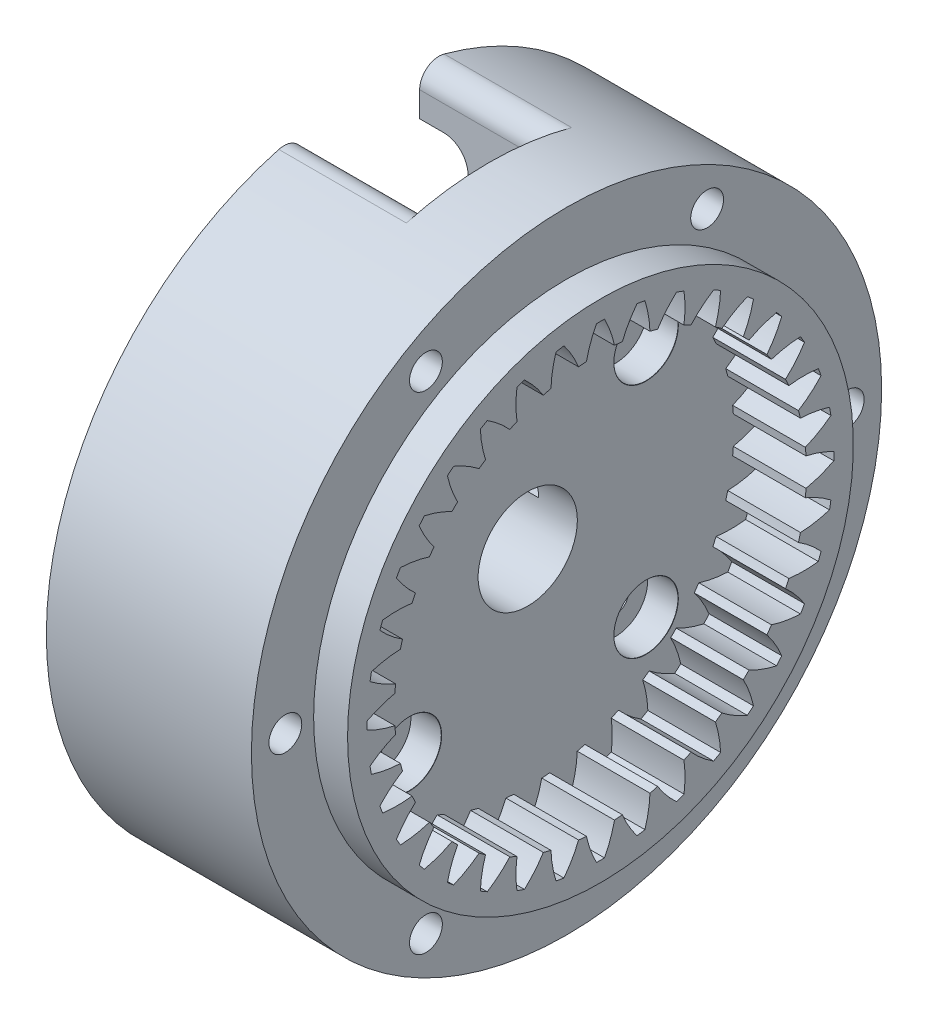
SolidWorks part; units mm, degrees
other "Markup1"
sketch "Sketch48"
ref_plane "Plane1" through (0, 0, 0) normal (0, 0, 1) x (1, 0, 0)
ref_plane "Plane2" through (0, 0, 0) normal (0, 1, 0) x (1, 0, 0)
ref_plane "Plane3" through (0, 0, 0) normal (1, 0, 0) x (0, 0, -1)
sketch "HoldingSke" plane through (0, 0, 0) normal (0, 1, 0) x (1, 0, 0)
  line L0 (0, 0) -> (328.7845, -238.8759)
  line L1 (-15, 0) -> (100, 0) construction
  line L2 (0, 0) -> (-2.1039, 2.3779)
  line L3 (0, 0) -> (-11.863, 4.5341)
  line L4 (0, 0) -> (6.9867, 5.0761)
  line L5 (0, 0) -> (-23.7986, -8.8762)
  line L6 (0, 0) -> (-10.5278, -7.1032)
  line L7 (-2.1039, 2.3779) -> (3.3635, 27.1825)
  line L8 (-76.2, 54.61) -> (-54.61, 54.61)
  line L9 (-67.7845, 28.3722) -> (-49.3413, 33.142)
  line L10 (-76.2, 71.12) -> (104.1128, 71.12)
  line L11 (0, 0) -> (-9.525, 0)
  line L12 (-76.2, 101.6) -> (-76.1428, 101.6)
  line L13 (24.9733, 27.94) -> (52.9518, 28.4284)
  line L14 (24.9733, 27.94) -> (24.9746, 27.94)
  line L15 (24.9733, 27.94) -> (100.4006, 29.5858)
  circle A0 centre (0, 0) radius 12.7
  circle A1 centre (0, 0) radius 12.7
  circle A2 centre (0, 0) radius 12.7
  dimension "MHD" = 25.4
  dimension "Hub_dia" = 25.4
  dimension "Diameter" = 25.4
  dimension "Num_teeth" = 36
  dimension "Pitch" = 406.4
  dimension "Overall_len" = 25.4
  dimension "Show_teeth" = 36
  dimension "Thickness" = 12.7
  dimension "OAL" = 25.4001
  dimension "T_dim" = 21.59
  dimension "Ap" = 14.5
  dimension "H" = 19.05
  dimension "Pitch_radius" = 180.3128
  dimension "Width" = 9.525
  dimension "Backlash" = 0.0571
  dimension "Addendum_fac" = 1
  dimension "Dedendum_fac" = 1.25
  dimension "Clearance_fac" = 0.25
  dimension "Dedendum_add" = 0.0013
sketch "BasProSke" plane through (0, 0, 0) normal (0, 1, 0) x (1, 0, 0)
  line L0 (-10, 0) -> (60, 0) construction
  line L1 (0, 26.9875) -> (0, 30.586)
  line L2 (0, 26.9875) -> (9.525, 26.9875)
  line L3 (9.525, 26.9875) -> (9.525, 30.586)
  line L4 (9.525, 30.586) -> (0, 30.586)
  dimension "Thickness" = 9.525
  dimension "Diameter" = 61.1721
  dimension "Inside_diameter" = 53.975
revolve "Base-Revolve" add sketch "BasProSke" angle 360 about L0
sketch "TooCutSke" plane through (0, 0, 0) normal (1, 0, 0) x (0, 0, -1)
  line L3 (1.3893, 28.5412) -> (1.3893, 53.6633) construction
  line L4 (0, 0) -> (0, 59.563) construction
  line L5 (0, 0) -> (-5.9551, 68.0675) construction
  line L6 (-12.1342, 23.9318) -> (35.5288, 28.1018) construction
  circle A0 centre (0, 0) radius 28.575 construction
  circle A1 centre (0, 0) radius 30.5606 construction
  circle A2 centre (0, 0) radius 24.8983 construction
  circle A3 centre (0, 0) radius 26.9621 construction
  arc A4 (1.8417, 26.8991) -> (0.5248, 30.5561) centre (-12.1342, 23.9318) ccw
  arc A5 (1.8417, 26.8991) -> (-1.8417, 26.8991) centre (0, 0) ccw
  arc A6 (0.5248, 30.5561) -> (-0.5248, 30.5561) centre (0, 0) ccw
  arc A7 (-0.5248, 30.5561) -> (-1.8417, 26.8991) centre (12.1342, 23.9318) ccw
  dimension "Pitch_dia" = 57.15
  dimension "Base_dia" = 49.7967
  dimension "Root_dia" = 61.1213
  dimension "Overcut_dia" = 53.9242
  dimension "Flank_rad" = 14.2875
  dimension "Half_ang" = 5
  dimension "Half_CT" = 1.3893
extrude "ToothCut" cut sketch "TooCutSke" along normal through all
fillet "Breaks" [suppressed] radius 0.1588
fillet "RootFillets" [suppressed] radius 0.3981
pattern_circular "TeethCuts" count 36 over 360 about axis through (0, 0, 0) along (1, 0, 0) of "RootFillets", "Breaks", "ToothCut"
sketch "Sketch3" plane through (0, 0, 0) normal (1, 0, 0) x (0, 0, -1)
  circle A0 centre (0, 0) radius 30.586 construction
  circle A1 centre (0, 0) radius 30.586
extrude "Extrude-Thin1" add sketch "Sketch3" along normal up to surface (9.525 mm away) thin
sketch "Sketch4" plane through (0, 0, 0) normal (1, 0, 0) x (0, 0, -1)
  circle A0 centre (0, 0) radius 33.126 construction
  circle A1 centre (0, 0) radius 33.126
extrude "Extrude-Thin2" add sketch "Sketch4" along normal blind 5.08 thin
sketch "Sketch5" plane through (0, 0, 0) normal (1, 0, 0) x (0, 0, -1)
  circle A0 centre (0, 0) radius 28.575 construction
  dimension "D1" = 57.15
sketch "Sketch9" plane through (0, 0, 0) normal (-1, 0, 0) x (0, 0, 1)
  circle A0 centre (0, 0) radius 59.944
  circle A1 centre (0, 0) radius 39.476 construction
  circle A2 centre (0, 0) radius 39.476
  dimension "D1" = 119.888
extrude "Boss-Extrude2" add sketch "Sketch9" against normal up to surface (5.08 mm away) up to face at (5.08, 0, -39.476)
sketch "Sketch12" plane through (0, 0, 0) normal (-1, 0, 0) x (0, 0, 1)
  circle A1 centre (0, 0) radius 59.944
  circle A5 centre (0, 0) radius 59.944
  dimension "D1" = 0
extrude "Boss-Extrude3" add sketch "Sketch12" along normal blind 5.08 contours A5
sketch "Sketch13" plane through (0, 0, 0) normal (1, 0, 0) x (0, 0, -1)
  circle A0 centre (0, 0) radius 20.2565
  circle A1 centre (0, 0) radius 17.9705
  dimension "D1" = 40.513
  dimension "D2" = 35.941
extrude "Cut-Extrude10" cut sketch "Sketch13" against normal blind 2.032
sketch "Sketch14" plane through (-5.08, 0, 0) normal (-1, 0, 0) x (0, 0, 1)
  circle A0 centre (0, 0) radius 3.302
  dimension "D1" = 6.604
extrude "Cut-Extrude11" cut sketch "Sketch14" against normal through all both and the other way through all
sketch "Sketch15" plane through (5.08, 0, 0) normal (1, 0, 0) x (0, 0, -1)
  circle A0 centre (0, 0) radius 47.498
  circle A1 centre (0, 0) radius 59.944 construction
  circle A2 centre (0, 0) radius 59.944
  dimension "D1" = 12.446
extrude "Boss-Extrude5" add sketch "Sketch15" along normal blind 14.605
sketch "Sketch16" plane through (19.685, 0, 0) normal (1, 0, 0) x (0, 0, -1)
  line L0 (0, 56.388) -> (0, 59.944) construction
  line L1 (0, 51.308) -> (0, 47.498) construction
  line L2 (56.388, 0) -> (59.944, 0) construction
  line L3 (51.308, 0) -> (47.498, 0) construction
  line L4 (0, -56.388) -> (0, -59.944) construction
  line L5 (0, -51.308) -> (0, -47.498) construction
  line L6 (-56.388, 0) -> (-59.944, 0) construction
  line L7 (-51.308, 0) -> (-47.498, 0) construction
  line L8 (0, 0) -> (-47.498, 0) construction
  circle A2 centre (0, 0) radius 59.944 construction
  circle A3 centre (0, 53.848) radius 2.54 construction
  circle A4 centre (0, 0) radius 47.498 construction
  circle A5 centre (53.848, 0) radius 2.54 construction
  circle A6 centre (0, -53.848) radius 2.54 construction
  circle A7 centre (-53.848, 0) radius 2.54 construction
  point P4 (0, 56.388)
  point P19 (56.388, 0)
  point P26 (0, -56.388)
  point P33 (-56.388, 0)
  point P38 (0, 0)
  dimension "D2" = 5.08
  dimension "D1" = 53.848
  dimension "D3" = 4
hole_wizard "CBORE for #00 Binding Head Machine Screw1" positions "Sketch18" profile "Sketch19" counterbore size "#00" standard "ANSI Inch" end condition through all
sketch "Sketch18" plane through (-5.08, 0, 0) normal (-1, 0, 0) x (0, 0, 1)
  point P0 (0, 53.848)
  point P3 (53.848, 0)
  point P6 (0, -53.848)
  point P9 (-53.848, 0)
sketch "Sketch19" plane through (-5.08, 53.848, 0) normal (0, 1, 0) x (0, 0, 1)
  line L0 (0, 0) -> (0, 24.765)
  line L1 (0, 24.765) -> (2.54, 24.765)
  line L3 (2.54, 24.765) -> (2.54, 1.27)
  line L4 (2.54, 1.27) -> (3.81, 1.27)
  line L5 (3.81, 1.27) -> (3.81, 0)
  line L7 (3.81, 0) -> (0, 0)
  line L11 (0, -6.35) -> (0, 107.95) construction
  dimension "Thru Hole Dia." = 5.08
  dimension "Thru Hole Depth" = 24.765
  dimension "C'Bore Dia." = 7.62
  dimension "C'Bore Depth" = 1.27
sketch "Sketch21" plane through (-5.08, 0, 0) normal (-1, 0, 0) x (0, 0, 1)
  circle A0 centre (0, 0) radius 19.05
  dimension "D1" = 38.1
extrude "Cut-Extrude12" cut sketch "Sketch21" against normal blind 1.524
sketch "Sketch22" plane through (-5.08, 0, 0) normal (-1, 0, 0) x (0, 0, 1)
  circle A0 centre (15.5, -15.5) radius 1.5 construction
  circle A1 centre (-15.5, -15.5) radius 1.5 construction
  circle A2 centre (-15.5, 15.5) radius 1.5 construction
  circle A3 centre (15.5, 15.5) radius 1.5 construction
  circle A5 centre (0, 0) radius 3.302 construction
  dimension "D1" = 31
  dimension "D4" = 15.5
  dimension "D5" = 3
  dimension "D2" = 31
  dimension "D3" = 15.5
sketch "Sketch26" plane through (-3.556, 0, 0) normal (-1, 0, 0) x (0, 0, 1)
  circle A0 centre (0, 0) radius 7.62
  dimension "D1" = 15.24
extrude "Cut-Extrude15" cut sketch "Sketch26" against normal through all
sketch "Sketch28" plane through (-3.556, 0, 0) normal (-1, 0, 0) x (0, 0, 1)
  circle A1 centre (0, 0) radius 19.05
  circle A2 centre (0, 0) radius 19.05
  circle M2 centre (0, 0) radius 7.62
  circle M3 centre (0, 0) radius 19.05
  dimension "D1" = 0
extrude "Boss-Extrude8" add sketch "Sketch28" along normal up to surface (1.524 mm away) contours M3 M2 up to face at (-5.08, 0, 19.05)
sketch "Sketch29" plane through (-5.08, 0, 0) normal (-1, 0, 0) x (0, 0, 1)
  circle A0 centre (0, 0) radius 44.45
  dimension "D1" = 88.9
extrude "Boss-Extrude9" add sketch "Sketch29" along normal blind 11.62
sketch "Sketch31" plane through (-16.7, 0, 0) normal (-1, 0, 0) x (0, 0, 1)
  line L0 (0, 0) -> (0, 59.944) construction
  line L2 (-7.62, 0) -> (7.62, 0)
  line L3 (-7.62, 0) -> (-7.62, 50.8)
  line L4 (-7.62, 50.8) -> (7.62, 50.8)
  line L5 (7.62, 0) -> (7.62, 50.8)
  line L6 (-7.62, 0) -> (7.62, 50.8) construction
  line L7 (-7.62, 50.8) -> (7.62, 0) construction
  circle A0 centre (0, 0) radius 59.944 construction
  circle A1 centre (0, 0) radius 7.62 construction
  point P6 (0, 25.4)
  dimension "D1" = 50.8
  dimension "D2" = 0
extrude "Cut-Extrude17" cut sketch "Sketch31" against normal up to surface (11.62 mm away) up to face at (-5.08, 0, 44.45)
sketch "Sketch32" plane through (-16.7, 0, 0) normal (-1, 0, 0) x (0, 0, 1)
  circle A0 centre (0, 0) radius 12.7
  dimension "D1" = 25.4
extrude "Cut-Extrude18" cut sketch "Sketch32" against normal blind 3.175
sketch "Sketch34" plane through (0, 0, 0) normal (1, 0, 0) x (0, 0, -1)
  line L3 (-11.3722, 58.8554) -> (-50.8, 51.237)
  line L4 (-11.3722, -58.8554) -> (-50.8, -51.237)
  line L5 (0, 0) -> (-203.2, 0) construction
  line L6 (-203.2, 41.275) -> (-203.2, -41.275)
  arc A0 (-203.2, -41.275) -> (-50.8, -51.237) centre (-166.4499, -649.7662) cw
  circle A2 centre (0, 0) radius 59.944 construction
  arc A3 (-203.2, 41.275) -> (-50.8, 51.237) centre (-166.4499, 649.7662) ccw
  arc A4 (-11.3722, 58.8554) -> (-11.3722, -58.8554) centre (0, 0) ccw
  point P12 (-203.2, 0)
  dimension "D2" = 609.6
  dimension "D1" = 203.2
  dimension "D3" = 82.55
  dimension "D4" = 50.8
sketch "Sketch38" plane through (-2.032, 0, 0) normal (1, 0, 0) x (0, 0, -1)
  circle A1 centre (0, 0) radius 20.2565
  circle A2 centre (0, 0) radius 20.2565
  circle M2 centre (0, 0) radius 17.9705
  circle M3 centre (0, 0) radius 20.2565
  dimension "D1" = 0
extrude "Boss-Extrude14" add sketch "Sketch38" along normal up to surface (2.032 mm away) contours M3 M2 up to face at (0, 0, -20.2565)
hole_wizard "CBORE for M3 Hex Head Machine Screw1" positions "Sketch39" profile "Sketch40" counterbore size "M3" standard "ANSI Metric" end condition through all
sketch "Sketch39" plane through (0, 0, 0) normal (1, 0, 0) x (0, 0, -1)
  point P0 (15.5, 15.5)
  point P3 (-15.5, 15.5)
  point P6 (-15.5, -15.5)
  point P9 (15.5, -15.5)
sketch "Sketch40" plane through (0, 15.5, -15.5) normal (0, 1, 0) x (0, 0, -1)
  line L0 (0, 0) -> (0, 16.7)
  line L1 (0, 16.7) -> (1.7, 16.7)
  line L3 (1.7, 16.7) -> (1.7, 4)
  line L4 (4.2, 4) -> (1.7, 4)
  line L5 (4.2, 4) -> (4.2, 0.025)
  line L6 (4.2, 0.025) -> (4.225, 0)
  line L7 (4.225, 0) -> (0, 0)
  line L8 (-4.2, 0.025) -> (-4.225, 0) construction
  line L11 (0, -6.35) -> (0, 107.95) construction
  dimension "Thru Hole Dia." = 3.4
  dimension "Thru Hole Depth" = 16.7
  dimension "C'Bore Dia." = 8.4
  dimension "C'Bore Depth" = 4
  dimension "Near C'Sink Dia." = 8.45
  dimension "Near C'Sink Angle" = 90
sketch "Sketch41" plane through (-5.08, 0, 0) normal (1, 0, 0) x (0, 0, -1)
  circle A0 centre (0, 0) radius 7.62 construction
  circle A1 centre (0, 0) radius 7.62
extrude "Cut-Extrude21" cut sketch "Sketch41" against normal through all
sketch "Sketch42" plane through (0, 0, 0) normal (1, 0, 0) x (0, 0, -1)
  circle A0 centre (0, 0) radius 3
  circle A1 centre (0, 0) radius 7.62 construction
  circle A2 centre (0, 0) radius 7.62
  dimension "D1" = 6
extrude "Boss-Extrude15" add sketch "Sketch42" against normal up to surface (13.525 mm away) contours A2 A0 up to face at (-13.525, -2.54, 0)
sketch "Sketch43" plane through (-5.08, 0, 0) normal (-1, 0, 0) x (0, 0, 1)
  line L0 (-7.62, 0) -> (-7.62, 10.16) construction
  line L1 (7.62, 43.792) -> (7.62, 0) construction
  line L2 (-7.62, 0) -> (-7.62, 10.16)
  line L3 (7.62, 10.16) -> (7.62, 0)
  arc A1 (7.62, 10.16) -> (-7.62, 10.16) centre (0, 0) ccw
  arc A4 (-7.62, 10.16) -> (7.62, 10.16) centre (0, 0) ccw construction
  arc A5 (7.62, 0) -> (-7.62, 0) centre (0, 0) ccw construction
  arc A6 (7.62, 0) -> (-7.62, 0) centre (0, 0) ccw
extrude "Boss-Extrude16" add sketch "Sketch43" along normal up to surface (8.445 mm away) up to face at (-13.525, 1.27, 0)
sketch "Sketch45" plane through (-13.525, 0, 0) normal (-1, 0, 0) x (0, 0, 1)
  line L0 (0, 0) -> (47.498, 0) construction
  line L1 (-3, 0) -> (3, 0)
  line L2 (-3, 0) -> (-3, 25.4)
  line L3 (-3, 25.4) -> (3, 25.4)
  line L4 (3, 0) -> (3, 25.4)
  circle A0 centre (0, 0) radius 3 construction
  dimension "D1" = 25.4
extrude "Cut-Extrude22" cut sketch "Sketch45" against normal up to surface (8.445 mm away) up to face at (-5.08, 53.848, 3.81)
sketch "Sketch46" plane through (-5.08, 0, 0) normal (-1, 0, 0) x (0, 0, 1)
  line L0 (7.62, 43.792) -> (7.62, 10.16) construction
  line L1 (7.62, 26.976) -> (-7.62, 26.976)
  line L2 (7.62, 26.976) -> (7.62, 0)
  line L3 (7.62, 0) -> (-7.62, 0)
  line L4 (-7.62, 26.976) -> (-7.62, 0)
  line L5 (-7.62, 43.792) -> (-7.62, 10.16) construction
  line L7 (0, 0) -> (47.498, 0) construction
extrude "Cut-Extrude23" cut sketch "Sketch46" along normal up to surface (8.445 mm away) up to face at (-13.525, 3.2684, 0)
sketch "Sketch47" plane through (0, 0, 0) normal (1, 0, 0) x (0, 0, -1)
  circle A0 centre (0, 0) radius 6.5
  dimension "D1" = 13
extrude "Cut-Extrude24" cut sketch "Sketch47" against normal up to surface (13.525 mm away)
sketch "Sketch49" plane through (19.685, 0, 0) normal (1, 0, 0) x (0, 0, -1)
  line L0 (0, 0) -> (0, 171.45) construction
  line L1 (-59.992, 160.6295) -> (-55.4107, 135.2295)
  line L4 (-59.1113, 9.9568) -> (-54.8329, 35.3568)
  line L7 (59.1113, 9.9568) -> (54.8329, 35.3568)
  line L8 (59.992, 160.6295) -> (55.4107, 135.2295)
  line L9 (-50.8, 85.3182) -> (50.8, 85.3182) construction
  circle A4 centre (0, 0) radius 59.944 construction
  arc A5 (59.944, 0) -> (59.1113, 9.9568) centre (0, 0) ccw construction
  arc A6 (59.992, 160.6295) -> (-59.992, 160.6295) centre (0, 171.45) ccw
  arc A7 (-54.8329, 35.3568) -> (-55.4107, 135.2295) centre (-341.4575, 83.6365) ccw
  arc A8 (54.8329, 35.3568) -> (55.4107, 135.2295) centre (341.4575, 83.6365) cw
  arc A9 (59.1113, 9.9568) -> (-59.1113, 9.9568) centre (0, 0) ccw
  arc A10 (-59.1113, 9.9568) -> (59.944, 0) centre (0, 0) ccw construction
  arc A11 (-59.1113, 9.9568) -> (59.944, 0) centre (0, 0) ccw construction
  arc A12 (59.944, 0) -> (59.1113, 9.9568) centre (0, 0) ccw construction
  dimension "D2" = 25.4
  dimension "D3" = 101.6
  dimension "D1" = 25.4
  dimension "D5" = 60.96
  dimension "D4" = 171.45
fillet "Fillet1" radius 2.54 1 edges at (-5.08, -44.45, 0)
sketch "Sketch50" plane through (5.08, 0, 0) normal (1, 0, 0) x (0, 0, -1)
  circle A0 centre (0, 0) radius 41.275
  dimension "D1" = 82.55
extrude "Cut-Extrude25" cut sketch "Sketch50" against normal through all flip side to cut
sketch "Sketch51" plane through (5.08, 0, 0) normal (1, 0, 0) x (0, 0, -1)
  line L0 (0, 0) -> (-38.1, 0) construction
  dimension "D1" = 38.1
sketch "Sketch54" plane through (5.08, 0, 0) normal (1, 0, 0) x (0, 0, -1)
  line L0 (0, 0) -> (-39.1456, 0) construction
sketch "Sketch56" plane through (-16.7, 0, 0) normal (-1, 0, 0) x (0, 0, 1)
  circle A0 centre (0, 0) radius 41.275
extrude "Cut-Extrude26" cut sketch "Sketch56" against normal blind 1.27
sketch "Sketch57" plane through (-15.43, 0, 0) normal (-1, 0, 0) x (0, 0, 1)
  line L0 (7.62, 40.5655) -> (7.62, 0) construction
  line L1 (-7.62, 0) -> (-7.62, 40.5655) construction
  line L2 (7.62, 40.5655) -> (7.62, 34.0836)
  line L3 (-7.62, 34.0836) -> (-7.62, 40.5655)
  arc A2 (-7.62, 34.0836) -> (7.62, 34.0836) centre (0, 0) ccw
  arc A3 (-7.62, 40.5655) -> (7.62, 40.5655) centre (0, 0) ccw construction
  arc A4 (-7.62, 40.5655) -> (7.62, 40.5655) centre (0, 0) ccw
  dimension "D1" = 6.35
extrude "Boss-Extrude17" add sketch "Sketch57" along normal blind 6.35
fillet "Fillet2" radius 2.54 2 edges at (-13.43, 40.5655, 7.62) (-13.43, 40.5655, -7.62)
fillet "Fillet3" radius 3.175 1 edges at (-15.43, -34.925, 0)
hole_wizard "M4 Clearance Hole1" positions "3DSketch3" profile "Sketch55" hole size "M4" standard "ANSI Metric" end condition through all
sketch3d "3DSketch3"
  line L0 (0, 0, 0) -> (0, 0, 36.83) construction
  line L1 (-13.525, 0, 0) -> (-5.08, 0, 0) construction
  line L3 (0, 0, 36.83) -> (5.08, 0, 36.83) construction
  point P0 (5.08, 0, 36.83)
  dimension "D1" = 36.83
sketch "Sketch55" plane through (5.08, 0, 36.83) normal (0, 1, 0) x (0, 0, -1)
  line L0 (0, 0) -> (0, 26.86)
  line L1 (0, 26.86) -> (2.15, 26.86)
  line L2 (2.15, 26.86) -> (2.15, 0)
  line L5 (2.15, 0) -> (0, 0)
  line L11 (0, -6.35) -> (0, 107.95) construction
  dimension "Thru Hole Dia." = 4.3
  dimension "Thru Hole Depth" = 26.86
pattern_circular "CirPattern1" count 6 over 360 about axis through (0, 0, 0) along (1, 0, 0) of "M4 Clearance Hole1"
equation "' \"Pitch@HoldingSke\" = 4"
equation "' \"Num_teeth@HoldingSke\" = 24"
equation "' \"Ap@HoldingSke\" =  14.5"
equation "' \"Ap@HoldingSke\" = 14.5"
equation "' \"Width@HoldingSke\" = 0.5"
equation "' \"Diameter@HoldingSke\" = 8"
equation "' \"Show_teeth@HoldingSke\" = 100"
equation "' \"Backlash@HoldingSke\" = 0.009"
equation "' \"Addendum_fac@HoldingSke\" = 1.0"
equation "' \"Dedendum_fac@HoldingSke\" = 1.25"
equation "' \"Dedendum_add@HoldingSke\" = 0.00005"
equation "' \"Clearance_fac@HoldingSke\" = 0.25"
equation "\"Overcut_dia@TooCutSke\" = (\"Num_teeth@HoldingSke\" - 2 * \"Addendum_fac@HoldingSke\") / \"Pitch@HoldingSke\" - 0.002"
equation "\"Pitch_dia@TooCutSke\" = \"Num_teeth@HoldingSke\" / \"Pitch@HoldingSke\""
equation "\"Base_dia@TooCutSke\" = \"Num_teeth@HoldingSke\" / \"Pitch@HoldingSke\" * cos((\"Ap@HoldingSke\"  * 3.14159265 / 180)) * 0.90"
equation "\"Root_dia@TooCutSke\" = \"Num_teeth@HoldingSke\"  / \"Pitch@HoldingSke\" + 2 *  \"Dedendum_fac@HoldingSke\"/ \"Pitch@HoldingSke\" + \"Dedendum_add@HoldingSke\" * 2"
equation "\"Half_ang@TooCutSke\" = 180 / \"Num_teeth@HoldingSke\""
equation "\"Half_CT@TooCutSke\" = \"Num_teeth@HoldingSke\" / \"Pitch@HoldingSke\" * sin((3.14159265 / 2 / \"Num_teeth@HoldingSke\")) / 2 + 10 * \"Backlash@HoldingSke\" / 4"
equation "\"Flank_rad@TooCutSke\" = \"Num_teeth@HoldingSke\" / \"Pitch@HoldingSke\" / 4"
equation "\"Radius@RootFillets\"= \"Clearance_fac@HoldingSke\" / \"Pitch@HoldingSke\" + \"Dedendum_add@HoldingSke\""
equation "\"Break_rad@Breaks\" = 0.02 / \"Pitch@HoldingSke\" * 5"
equation "\"Num_teeth@TeethCuts\" = int( \"Show_teeth@HoldingSke\" ) + 1"
equation "\"Num_teeth@TeethCuts\" = ((sgn( \"Num_teeth@TeethCuts\" - \"Num_teeth@HoldingSke\" )-1)*( \"Num_teeth@TeethCuts\" - \"Num_teeth@HoldingSke\" ))/-2+ \"Num_teeth@HoldingSke\""
equation "\"Num_teeth@TeethCuts\" = ((sgn( \"Num_teeth@TeethCuts\" - 2.0)+1)*( \"Num_teeth@TeethCuts\" - 2.0))/2 +2.0"
equation "\"Angle@TeethCuts\" = 360.0 / \"Num_teeth@HoldingSke\""
equation "\"Diameter@BasProSke\" = \"Num_teeth@HoldingSke\"  / \"Pitch@HoldingSke\" + 2 *  \"Dedendum_fac@HoldingSke\"/ \"Pitch@HoldingSke\" + \"Dedendum_add@HoldingSke\" * 2 + 0.002"
equation "\"Diameter@BasProSke\" = ((sgn( \"Diameter@BasProSke\"  - \"Diameter@HoldingSke\" )+1)*( \"Diameter@BasProSke\"  - \"Diameter@HoldingSke\" ))/2 + \"Diameter@HoldingSke\""
equation "\"Inside_diameter@BasProSke\" =  (\"Num_teeth@HoldingSke\" - 2 * \"Addendum_fac@HoldingSke\") / \"Pitch@HoldingSke\" "
equation "\"Thickness@BasProSke\"  = \"Width@HoldingSke\""
